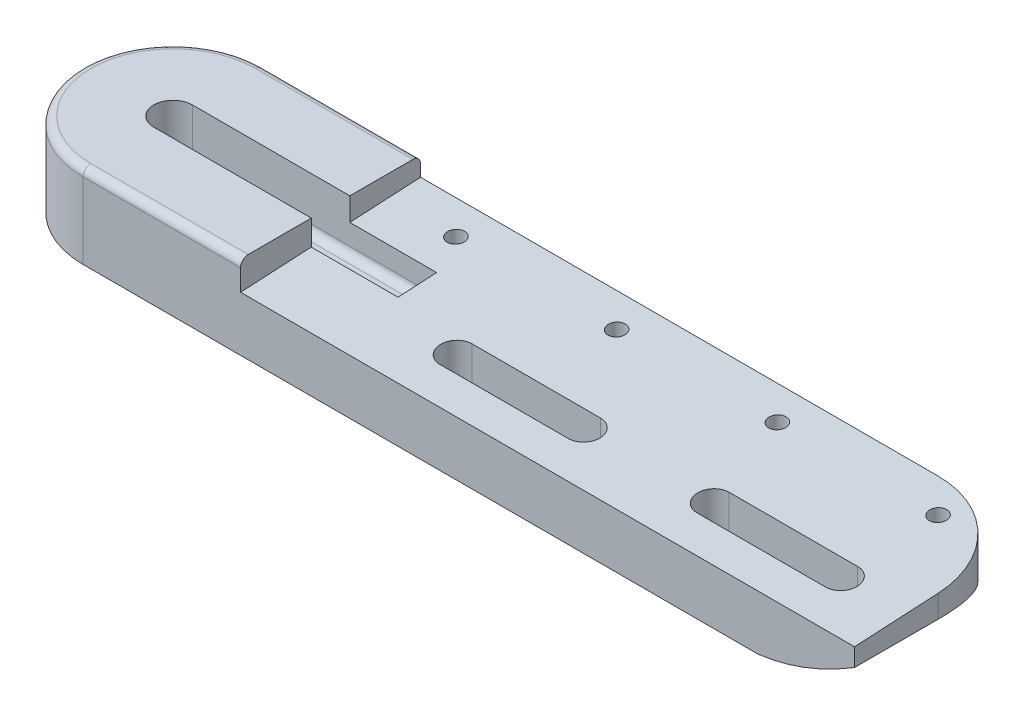
SolidWorks part; units mm, degrees
ref_plane "Front Plane" through (0, 0, 0) normal (0, 0, 1) x (1, 0, 0)
ref_plane "Top Plane" through (0, 0, 0) normal (0, 1, 0) x (1, 0, 0)
ref_plane "Right Plane" through (0, 0, 0) normal (1, 0, 0) x (0, 0, -1)
sketch "Sketch1" plane through (0, 0, 0) normal (0, 1, 0) x (1, 0, 0)
  line L0 (0, 3) -> (0, 2.4) construction
  line L2 (0, 14) -> (120, 14)
  line L7 (120, 14) -> (120, -14)
  line L8 (120, -14) -> (0, -14)
  line L9 (60, -14) -> (60, -6) construction
  line L10 (60, -6) -> (100, -6) construction
  line L11 (70, -6) -> (50, -6) construction
  line L13 (70, -8.5) -> (50, -8.5)
  line L14 (70, -3.5) -> (50, -3.5)
  line L15 (90, -6) -> (110, -6) construction
  line L16 (90, -3.5) -> (110, -3.5)
  line L17 (90, -8.5) -> (110, -8.5)
  line L20 (60, 14) -> (60, 9) construction
  line L21 (60, 9) -> (110, 9) construction
  arc A1 (0, 14) -> (0, -14) centre (0, 0) ccw
  arc A2 (70, -8.5) -> (70, -3.5) centre (70, -6) ccw
  arc A3 (50, -3.5) -> (50, -8.5) centre (50, -6) ccw
  arc A4 (90, -3.5) -> (90, -8.5) centre (90, -6) ccw
  arc A5 (110, -8.5) -> (110, -3.5) centre (110, -6) ccw
  circle A8 centre (85, 9) radius 1.35
  circle A9 centre (60, 9) radius 1.35
  circle A10 centre (110, 9) radius 1.35
  circle A11 centre (10, 9) radius 1.35
  circle A12 centre (35, 9) radius 1.35
  circle A13 centre (0, 0) radius 3
  point P9 (0, 2.4)
  point P18 (60, -6)
  point P25 (100, -6)
  dimension "D1" = 28
  dimension "D3" = 0.6
  dimension "D4" = 3
  dimension "D5" = 120
  dimension "D6" = 28
  dimension "D7" = 8
  dimension "D8" = 5
  dimension "D9" = 50
extrude "Boss-Extrude1" add sketch "Sketch1" along normal blind 10
sketch "Sketch9" plane through (0, 10, 0) normal (0, 1, 0) x (1, 0, 0)
  line L0 (0, -14) -> (120, -14) construction
  line L1 (0, 14) -> (24.5, 14)
  line L3 (0, -14) -> (24.5, -14)
  line L4 (24.5, 14) -> (24.5, -14)
  circle A0 centre (0, 0) radius 3
  arc A1 (0, 14) -> (0, -14) centre (0, 0) ccw
  dimension "D1" = 24.5
extrude "Boss-Extrude2" add sketch "Sketch9" along normal blind 3
sketch "Sketch10" plane through (0, 13, 0) normal (0, 1, 0) x (1, 0, 0)
  line L5 (0, 3) -> (38, 3)
  line L6 (0, 3) -> (0, -3)
  line L7 (0, -3) -> (38, -3)
  line L8 (38, 3) -> (38, -3)
  circle A1 centre (0, 0) radius 3 construction
  dimension "D1" = 38
  dimension "D2" = 6
extrude "Cut-Extrude3" cut sketch "Sketch10" against normal blind 8
sketch "Sketch4" plane through (120, 0, 0) normal (1, 0, 0) x (0, 0, -1)
  line L0 (-14, 10) -> (-14, 8.5)
  line L1 (-14, 10) -> (-14, 0) construction
  line L3 (-14, 10) -> (14, 10)
  line L4 (-14, 8.5) -> (14, 10)
  dimension "D1" = 1.5
fillet "Fillet3" radius 15 1 edges at (120, 5, -14)
fillet "Fillet4" radius 1.2 2 edges at (19, 5, 3) (19, 5, -3)
extrude "Cut-Extrude4" cut sketch "Sketch4" against normal up to surface (95.5 mm away) up to face at (24.5, 11.5, 8.5)
sketch "Sketch11" plane through (0, 0, -14) normal (0, 0, -1) x (-1, 0, 0)
  line L0 (-120, 9.1964) -> (-120, 5.6964)
  line L1 (-120, 0) -> (-120, 9.1964) construction
  line L2 (-120, 5.6964) -> (-120, 0)
  line L3 (-120, 0) -> (-105, 0)
  spline S0 degree 2 poles (-120, 5.6964) (-112.0758, 0.8452) (-105, 0) knots 0 0 0 0.273587 0.273587 0.273587
  dimension "D1" = 3.5
extrude "Cut-Extrude5" cut sketch "Sketch11" against normal blind 56 contours S0 L2 L3 region at (115.7103, 1.748, -14)
sketch "Sketch13" plane through (0, 0, 0) normal (0, -1, 0) x (1, 0, 0)
  circle A0 centre (0, 0) radius 3
  circle A1 centre (0, 0) radius 1.6
  dimension "D1" = 3.2
extrude "Boss-Extrude3" add sketch "Sketch13" against normal up to surface (5 mm away) up to face at (20.35, 5, 0)
fillet "Fillet5" radius 1.2 3 edges at (12.25, 13, -14) (-14, 13, 0) (12.25, 13, 14)
sketch "Sketch14" plane through (120, 0, 0) normal (1, 0, 0) x (0, 0, -1)
  line L0 (14, 0) -> (11.5, 0)
  line L1 (-3.5, 0) -> (14, 0) construction
  line L2 (14, 0) -> (14, 3)
  line L3 (14, 10) -> (14, 0) construction
  spline S0 degree 2 poles (11.5, 0) (13.1013, 0.7826) (14, 3) knots 0 0 0 0.269081 0.269081 0.269081
  dimension "D1" = 3
  dimension "D2" = 2.5
extrude "Cut-Extrude6" cut sketch "Sketch14" against normal blind 160.5
